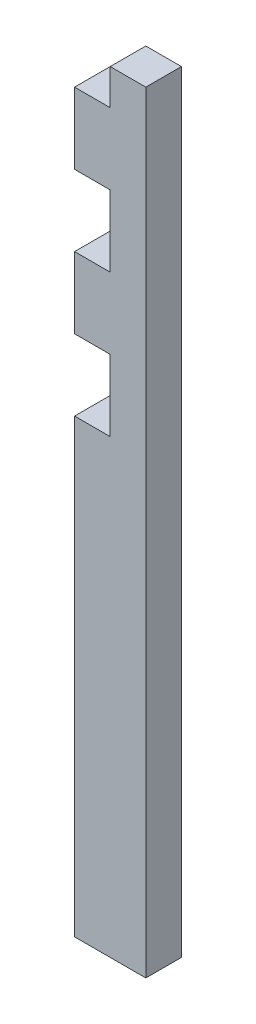
SolidWorks part; units mm, degrees
ref_plane "Front Plane" through (0, 0, 0) normal (0, 0, 1) x (1, 0, 0)
ref_plane "Top Plane" through (0, 0, 0) normal (0, 1, 0) x (1, 0, 0)
ref_plane "Right Plane" through (0, 0, 0) normal (1, 0, 0) x (0, 0, -1)
sketch "Sketch1" plane through (0, 0, 0) normal (0, 0, 1) x (1, 0, 0)
  line L3 (12, 0) -> (0, 0)
  line L4 (0, 0) -> (0, -30)
  line L5 (0, -30) -> (12, -30)
  line L6 (12, -30) -> (12, 0)
  line L9 (0, 0) -> (20, 0)
  line L26 (0, 0) -> (0, -30)
  line L28 (12, 0) -> (0, 0)
  line L29 (12, 0) -> (12, 100)
  line L30 (12, 100) -> (0, 100)
  line L31 (0, 0) -> (0, 100)
  dimension "D1" = 12
  dimension "D2" = 100
  dimension "D3" = 12
  dimension "D4" = 30
extrude "Boss-Extrude4" add sketch "Sketch1" along normal blind 6 contours L31 L3 region at (6, 50, 0)
extrude "Boss-Extrude5" add sketch "Sketch1<8>" along normal blind 6 contours L5 L6 L3 L4 region at (6, -15, 0)
sketch "Sketch1<8>" plane through (0, 0, 0) normal (0, 0, 1) x (1, 0, 0) same geometry as "Sketch1"
sketch "Sketch3" plane through (0, 0, 6) normal (0, 0, 1) x (1, 0, 0)
  line L1 (0, -10) -> (12, -10)
  line L2 (0, -10) -> (0, -20)
  line L3 (0, -20) -> (12, -20)
  line L4 (12, -10) -> (12, -20)
  line L5 (12, -30) -> (12, 100) construction
  dimension "D1" = 10
  dimension "D2" = 10
sketch "Sketch4" plane through (0, 0, 0) normal (0, 0, -1) x (-1, 0, 0)
  line L1 (0, 106) -> (-6, 106)
  line L2 (0, 106) -> (0, 94)
  line L3 (0, 94) -> (-6, 94)
  line L4 (-6, 106) -> (-6, 94)
  line L6 (-12, 100) -> (0, 100) construction
  line L7 (0, -30) -> (0, 100) construction
  line L8 (0, 82) -> (0, 70)
  line L9 (0, 82) -> (-6, 82)
  line L10 (-6, 82) -> (-6, 70)
  line L11 (0, 70) -> (-6, 70)
  line L12 (0, 58) -> (0, 46)
  line L13 (0, 58) -> (-6, 58)
  line L14 (-6, 58) -> (-6, 46)
  line L15 (0, 46) -> (-6, 46)
  dimension "D1" = 6
  dimension "D2" = 12
  dimension "D3" = 6
  dimension "D4" = 3
extrude "Cut-Extrude1" cut sketch "Sketch4" against normal up to next
